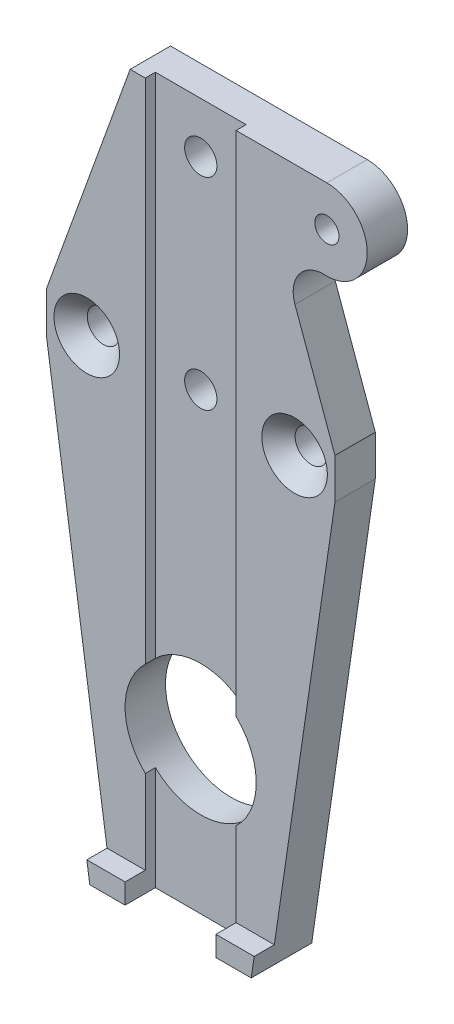
SolidWorks part; units mm, degrees
note: The reader was unsure of these and kept them because the rebuilt part matched: shared geometry of "Model<11>", "Model<12>".
ref_plane "前视基准面" through (0, 0, 0) normal (0, 0, 1) x (1, 0, 0)
ref_plane "上视基准面" through (0, 0, 0) normal (0, 1, 0) x (1, 0, 0)
ref_plane "右视基准面" through (0, 0, 0) normal (1, 0, 0) x (0, 0, -1)
sketch "Model" plane through (0, 0, 0) normal (0, 0, 1) x (1, 0, 0)
  line L0 (37.0406, 24.4545) -> (36.6995, 24.4545)
  line L1 (33.8777, 20.4362) -> (37.8406, 9.4545)
  line L2 (37.8406, 5.4545) -> (37.8406, 9.4545)
  line L3 (31.5406, -37.5455) -> (37.8406, 5.4545)
  line L4 (28.0406, -35.5455) -> (31.8336, -35.5455)
  line L5 (28.0406, -37.5455) -> (28.0406, -27.2359)
  line L6 (28.0406, -17.855) -> (28.0406, 32.4545)
  line L7 (19.0406, -17.855) -> (19.0406, 32.4545)
  line L8 (19.0406, -37.5455) -> (19.0406, -27.2359)
  line L9 (15.5406, -37.5455) -> (9.2406, 5.4545)
  line L10 (9.2406, 5.4545) -> (9.2406, 9.4545)
  line L11 (17.5406, 32.4545) -> (9.2406, 9.4545)
  line L12 (17.5406, 32.4545) -> (37.0406, 32.4545)
  line L13 (31.5406, -37.5455) -> (15.5406, -37.5455)
  line L14 (19.0406, -35.5455) -> (15.2476, -35.5455)
  circle A0 centre (33.8406, 7.4545) radius 3.245
  circle A1 centre (37.0406, 28.4545) radius 1.2
  arc A2 (36.6995, 24.4545) -> (33.8777, 20.4362) centre (36.6995, 21.4545) ccw
  arc A3 (37.0406, 24.4545) -> (37.0406, 32.4545) centre (37.0406, 28.4545) ccw
  circle A4 centre (23.5406, 27.4545) radius 1.6
  circle A5 centre (23.5406, 7.4545) radius 1.6
  circle A6 centre (13.2406, 7.4545) radius 3.245
  circle A7 centre (23.5406, -22.5455) radius 6.5
  circle A8 centre (13.2406, 7.4545) radius 1.6
  circle A9 centre (33.8406, 7.4545) radius 1.6
extrude "凸台-拉伸1" add sketch "Model" along normal blind 4 contours A7 L7 L12 L11 L10 L9 L14 L8 A6 | A7 L5 L4 L3 L2 L1 A2 L0 A3 L12 L6 A0 A1 | A8 | A0 A9 | A9
extrude "凸台-拉伸3" add sketch "Model<11>" along normal blind 3 contours A7 L6 L12 L7 A4 A5 | A7 L8 L13 L5 | L8 L14 L9 L13 | L13 L3 L4 L5
sketch "Model<11>" plane through (0, 0, 0) normal (0, 0, 1) x (1, 0, 0) same geometry as "Model"
extrude "凸台-拉伸4" add sketch "Model<12>" along normal blind 6 contours L8 L14 L9 L13 | L13 L3 L4 L5
sketch "Model<12>" plane through (0, 0, 0) normal (0, 0, 1) x (1, 0, 0) same geometry as "Model"
chamfer "倒角1" distance 1.65 angle 45 2 edges at (35.4406, 7.4545, 4) (14.8406, 7.4545, 4)
